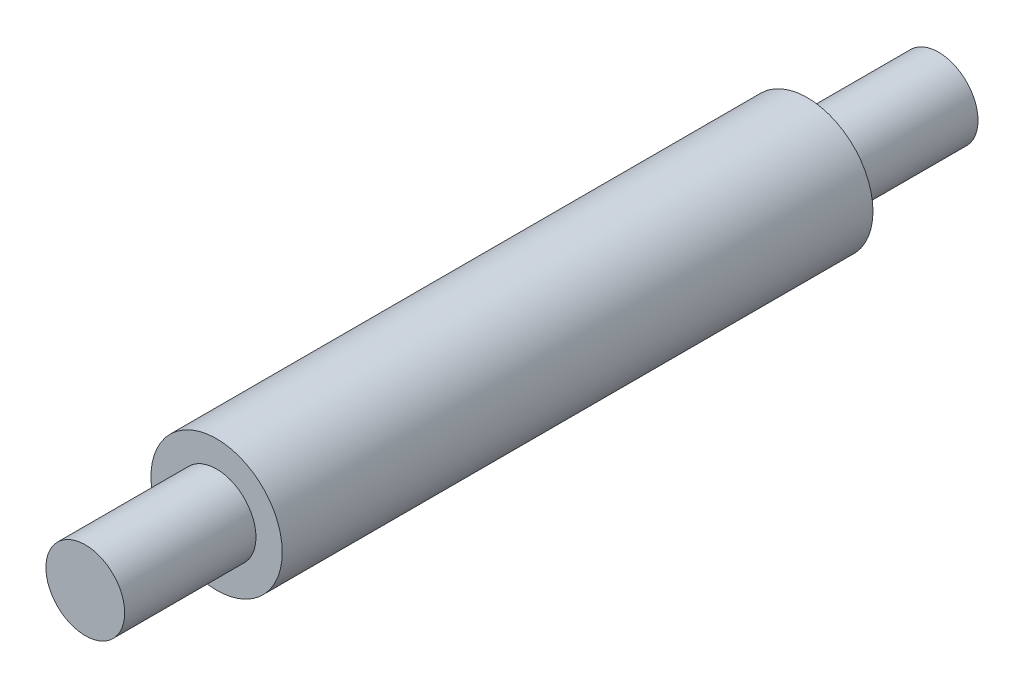
SolidWorks part; units mm, degrees
material "1060 Alloy"
ref_plane "Front Plane" through (0, 0, 0) normal (0, 0, 1) x (1, 0, 0)
ref_plane "Top Plane" through (0, 0, 0) normal (0, 1, 0) x (1, 0, 0)
ref_plane "Right Plane" through (0, 0, 0) normal (1, 0, 0) x (0, 0, -1)
sketch "Sketch6" plane through (0, 0, 0) normal (1, 0, 0) x (0, 0, -1)
  line L0 (0, 0) -> (65, 0)
  line L1 (65, 0) -> (65, 3)
  line L2 (65, 3) -> (55, 3)
  line L3 (55, 3) -> (55, 5)
  line L4 (55, 5) -> (10, 5)
  line L5 (10, 5) -> (10, 3)
  line L6 (10, 3) -> (0, 3)
  line L7 (0, 3) -> (0, 0)
  dimension "D1" = 10
  dimension "D2" = 3
  dimension "D3" = 5
  dimension "D4" = 45
revolve "Revolve1" add sketch "Sketch6" angle 360 about L0
